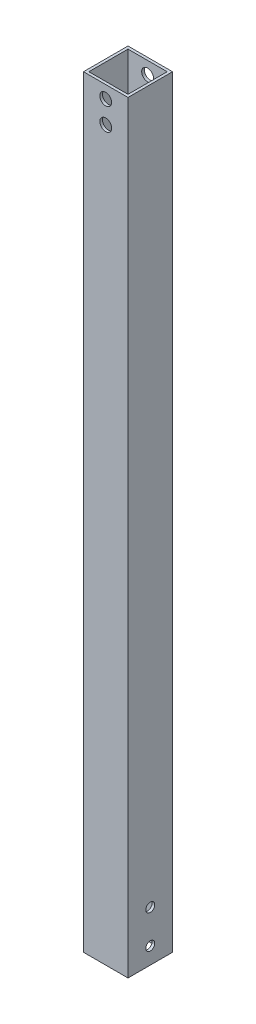
SolidWorks part; units mm, degrees
material "6061 Alloy"
ref_plane "Front Plane" through (0, 0, 0) normal (0, 0, 1) x (1, 0, 0)
ref_plane "Top Plane" through (0, 0, 0) normal (0, 1, 0) x (1, 0, 0)
ref_plane "Right Plane" through (0, 0, 0) normal (1, 0, 0) x (0, 0, -1)
sketch "Sketch1" plane through (0, 0, 0) normal (0, 1, 0) x (1, 0, 0)
  line L9 (12.7, -12.7) -> (-12.7, -12.7)
  line L10 (12.7, -12.7) -> (12.7, 12.7)
  line L11 (12.7, 12.7) -> (-12.7, 12.7)
  line L12 (-12.7, -12.7) -> (-12.7, 12.7)
  line L13 (12.7, -12.7) -> (-12.7, 12.7) construction
  line L14 (12.7, 12.7) -> (-12.7, -12.7) construction
  point P0 (0, 0)
  dimension "D1" = 25.4
extrude "Extrude-Thin1" add sketch "Sketch1" along normal blind 434.975 thin thin type one direction reverse wall 1.524
hole_wizard "1/4 Clearance Hole1" positions "Sketch2" profile "Sketch3" hole size "1/4" standard "ANSI Inch" end condition through all
sketch "Sketch2" plane through (0, 0, -12.7) normal (0, 0, -1) x (-1, 0, 0)
  point P0 (0, 427.7995)
  point P3 (0, 415.0995)
sketch "Sketch3" plane through (0, 427.7995, -12.7) normal (1, 0, 0) x (0, 1, 0)
  line L0 (0, 0) -> (0, 25.4)
  line L1 (0, 25.4) -> (3.3782, 25.4)
  line L2 (3.3782, 25.4) -> (3.3782, 0)
  line L5 (3.3782, 0) -> (0, 0)
  line L11 (0, -6.35) -> (0, 107.95) construction
  dimension "Thru Hole Dia." = 6.7564
  dimension "Thru Hole Depth" = 25.4
sketch "Sketch4" plane through (12.7, 0, 0) normal (1, 0, 0) x (0, 0, -1)
  line L0 (-12.7, 0) -> (12.7, 0) construction
  circle A0 centre (0, 9.525) radius 2.54
  circle A1 centre (0, 28.575) radius 2.54
  dimension "D1" = 5.08
  dimension "D2" = 9.525
  dimension "D3" = 28.575
hole_wizard "#10 Clearance Hole1" positions "Sketch5" profile "Sketch6" hole size "#10" standard "ANSI Inch" end condition through all
sketch "Sketch5" plane through (12.7, 0, 0) normal (1, 0, 0) x (0, 0, -1)
  point P0 (0, 9.525)
  point P3 (0, 28.575)
sketch "Sketch6" plane through (12.7, 9.525, 0) normal (0, 1, 0) x (0, 0, -1)
  line L0 (0, 0) -> (0, 25.4)
  line L1 (0, 25.4) -> (2.5527, 25.4)
  line L2 (2.5527, 25.4) -> (2.5527, 0)
  line L5 (2.5527, 0) -> (0, 0)
  line L11 (0, -6.35) -> (0, 107.95) construction
  dimension "Thru Hole Dia." = 5.1054
  dimension "Thru Hole Depth" = 25.4
